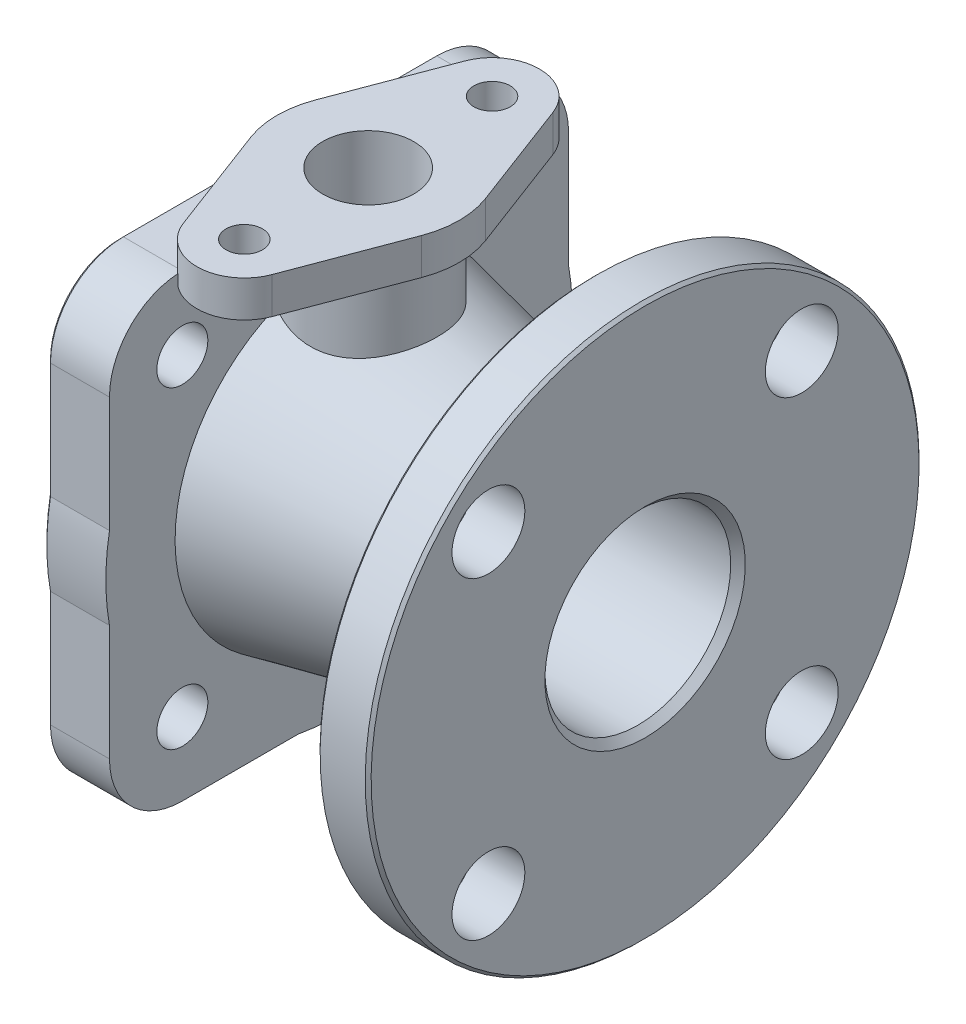
SolidWorks part; units mm, degrees
ref_plane "Front Plane" through (0, 0, 0) normal (0, 0, 1) x (1, 0, 0)
ref_plane "Top Plane" through (0, 0, 0) normal (0, 1, 0) x (1, 0, 0)
ref_plane "Right Plane" through (0, 0, 0) normal (1, 0, 0) x (0, 0, -1)
sketch "Sketch1" plane through (0, 0, 0) normal (1, 0, 0) x (0, 0, -1)
  line L0 (0, 23.0618) -> (0, -20.6537) construction
  line L1 (-18.3792, 0) -> (23.2988, 0) construction
  line L2 (43, 63) -> (11.2694, 63)
  line L3 (-63, 43) -> (-63, 11.2694)
  line L4 (63, 43) -> (63, 11.2694)
  line L5 (-43, 63) -> (-11.2694, 63)
  line L6 (-43, -63) -> (-11.2694, -63)
  line L7 (63, -43) -> (63, -11.2694)
  line L8 (-63, -43) -> (-63, -11.2694)
  line L9 (43, -63) -> (11.2694, -63)
  arc A0 (-63, 11.2694) -> (-63, -11.2694) centre (0, 0) ccw
  arc A1 (-43, 63) -> (-63, 43) centre (-43, 43) ccw
  arc A2 (43, 63) -> (63, 43) centre (43, 43) cw
  arc A3 (43, -63) -> (63, -43) centre (43, -43) ccw
  arc A4 (-43, -63) -> (-63, -43) centre (-43, -43) cw
  arc A5 (-11.2694, -63) -> (11.2694, -63) centre (0, 0) ccw
  arc A6 (63, -11.2694) -> (63, 11.2694) centre (0, 0) ccw
  arc A7 (11.2694, 63) -> (-11.2694, 63) centre (0, 0) ccw
  dimension "D1" = 128
  dimension "D2" = 40
  dimension "D3" = 43
  dimension "D4" = 43
extrude "Boss-Extrude1" add sketch "Sketch1" against normal blind 17
sketch "Sketch3" plane through (0, 0, 0) normal (0, 0, 1) x (1, 0, 0)
  line L0 (0, 0) -> (0, 45)
  line L1 (0, 43) -> (0, 11.2694) construction
  line L2 (0, 45) -> (50, 34.5)
  line L3 (50, 34.5) -> (70, 34.5)
  line L4 (70, 34.5) -> (70, 76)
  line L5 (70, 76) -> (84, 76)
  line L6 (84, 76) -> (84, 0)
  line L7 (84, 0) -> (0, 0)
  line L8 (0, 43) -> (0, 63) construction
  dimension "D1" = 76
  dimension "D2" = 34.5
  dimension "D3" = 45
  dimension "D4" = 14
  dimension "D5" = 34
  dimension "D6" = 70
revolve "Revolve1" add sketch "Sketch3" angle 360 about L7
sketch "Sketch4" plane through (-17, 0, 0) normal (-1, 0, 0) x (0, 0, 1)
  line L0 (0, 18.2893) -> (0, -17.4337) construction
  line L1 (-19.145, 0) -> (17.4337, 0) construction
  circle A0 centre (-43, 43) radius 7
  circle A1 centre (43, 43) radius 7
  circle A2 centre (43, -43) radius 7
  circle A3 centre (-43, -43) radius 7
  dimension "D1" = 14
extrude "Cut-Extrude1" cut sketch "Sketch4" against normal blind 17
sketch "Sketch5" plane through (84, 0, 0) normal (1, 0, 0) x (0, 0, -1)
  line L0 (0, 21.498) -> (0, -20.6423) construction
  line L1 (-17.6476, 0) -> (31.7657, 0) construction
  circle A0 centre (-43, 43) radius 10
  arc A1 (-43, 63) -> (-63, 43) centre (-43, 43) ccw construction
  circle A2 centre (43, 43) radius 10
  circle A3 centre (43, -43) radius 10
  circle A4 centre (-43, -43) radius 10
  dimension "D1" = 20
extrude "Cut-Extrude2" cut sketch "Sketch5" against normal blind 17
sketch "Sketch7" plane through (84, 0, 0) normal (1, 0, 0) x (0, 0, -1)
  circle A0 centre (0, 0) radius 25.5
  dimension "D1" = 51
extrude "Cut-Extrude3" cut sketch "Sketch7" against normal through all
sketch "Sketch8" plane through (0, 0, 0) normal (0, 1, 0) x (1, 0, 0)
  circle A0 centre (8, 0) radius 19
  dimension "D1" = 38
  dimension "D2" = 25
extrude "Boss-Extrude2" add sketch "Sketch8" along normal blind 70
sketch "Sketch9" plane through (0, 70, 0) normal (0, 1, 0) x (1, 0, 0)
  line L0 (-4.1634, 38.5882) -> (-15.3911, 8.8235)
  line L1 (8, 10.3747) -> (8, -11.2303) construction
  line L2 (17.9915, 0) -> (-4.1634, 0) construction
  line L3 (20.1634, 38.5882) -> (31.3911, 8.8235)
  line L4 (20.1634, -38.5882) -> (31.3911, -8.8235)
  line L5 (-4.1634, -38.5882) -> (-15.3911, -8.8235)
  arc A0 (-15.3911, 8.8235) -> (-15.3911, -8.8235) centre (8, 0) ccw
  arc A1 (20.1634, 38.5882) -> (-4.1634, 38.5882) centre (8, 34) ccw
  arc A2 (20.1634, -38.5882) -> (-4.1634, -38.5882) centre (8, -34) cw
  arc A3 (31.3911, -8.8235) -> (31.3911, 8.8235) centre (8, 0) ccw
  dimension "D1" = 50
  dimension "D2" = 26
  dimension "D3" = 34
extrude "Boss-Extrude3" add sketch "Sketch9" against normal blind 10
sketch "Sketch11" plane through (0, 70, 0) normal (0, 1, 0) x (1, 0, 0)
  line L0 (21.2002, 0) -> (-2.7578, 0) construction
  circle A0 centre (8, 34) radius 5
  circle A1 centre (8, -34) radius 5
  dimension "D1" = 10
extrude "Cut-Extrude4" cut sketch "Sketch11" against normal blind 10
sketch "Sketch12" plane through (0, 70, 0) normal (0, 1, 0) x (1, 0, 0)
  circle A0 centre (8, 0) radius 12.5
  dimension "D1" = 25
extrude "Cut-Extrude5" cut sketch "Sketch12" against normal up to surface (70 mm away) up to face at (8, 0, 19)
chamfer "Chamfer1" distance 2 angle 45 2 edges at (-17, 25.5, 0) (84, 25.5, 0)
fillet "Fillet1" radius 2 1 edges at (70, 34.5, 0)
chamfer "Chamfer2" distance 0.81 angle 45 17 edges at (-17, 0, 64) (-17, -27.1347, 63) (-17, -57.1421, 57.1421) (-17, -64, 0) (-17, -63, 27.1347) (-17, -63, -27.1347) (-17, -57.1421, -57.1421) (-17, -27.1347, -63) (-17, 0, -64) (-17, 27.1347, 63) (-17, 57.1421, 57.1421) (-17, 63, 27.1347) (-17, 27.1347, -63) (-17, 63.7495, 5.6569) (-17, 57.1421, -57.1421) (-17, 63.7495, -5.6569) (-17, 63, -27.1347)
chamfer "Chamfer3" distance 0.81 angle 45 2 edges at (70, 76, 0) (84, 76, 0)
